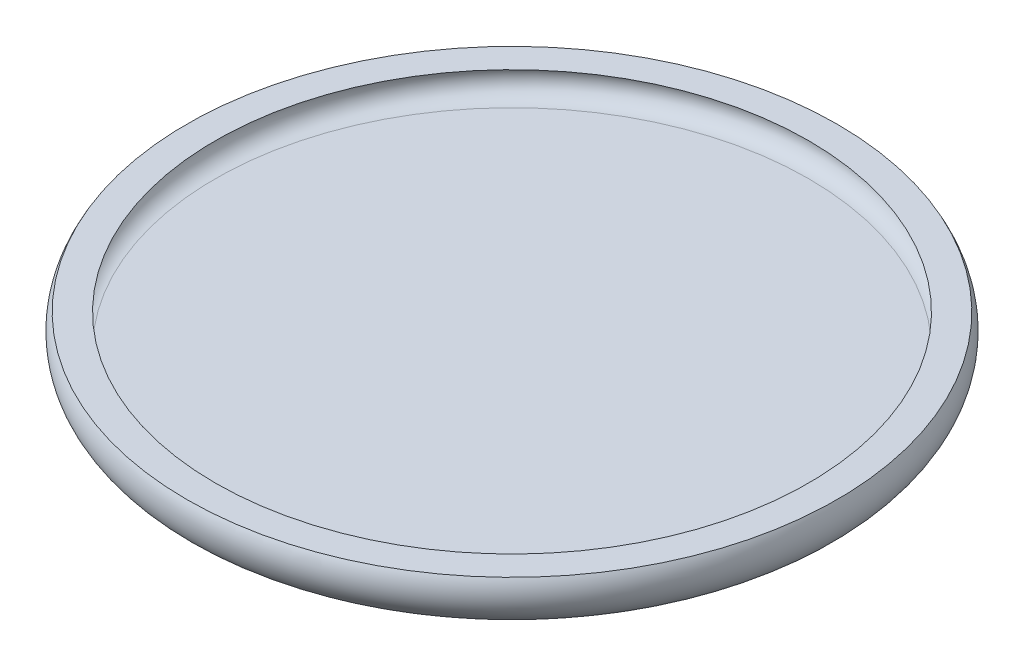
SolidWorks part; units mm, degrees
ref_plane "Front Plane" through (0, 0, 0) normal (0, 0, 1) x (1, 0, 0)
ref_plane "Top Plane" through (0, 0, 0) normal (0, 1, 0) x (1, 0, 0)
ref_plane "Right Plane" through (0, 0, 0) normal (1, 0, 0) x (0, 0, -1)
sketch "Sketch3" plane through (0, 0, 0) normal (0, 0, 1) x (1, 0, 0)
  line L4 (-18, 0) -> (0, 0)
  line L9 (-18, 1) -> (0, 1)
  line L10 (0, 0) -> (0, 1)
  line L11 (-18, 3) -> (-19.7321, 3)
  arc A1 (-18, 3) -> (-18, 1) centre (-18, 2) ccw
  arc A3 (-18, 0) -> (-19.7321, 3) centre (-18, 2) cw
  dimension "D1" = 3
  dimension "D2" = 18
  dimension "D3" = 2
  dimension "D4" = 1
revolve "Revolve1" add sketch "Sketch3" angle 360 about L10 region at (-10.6379, 0.6626, 0)
